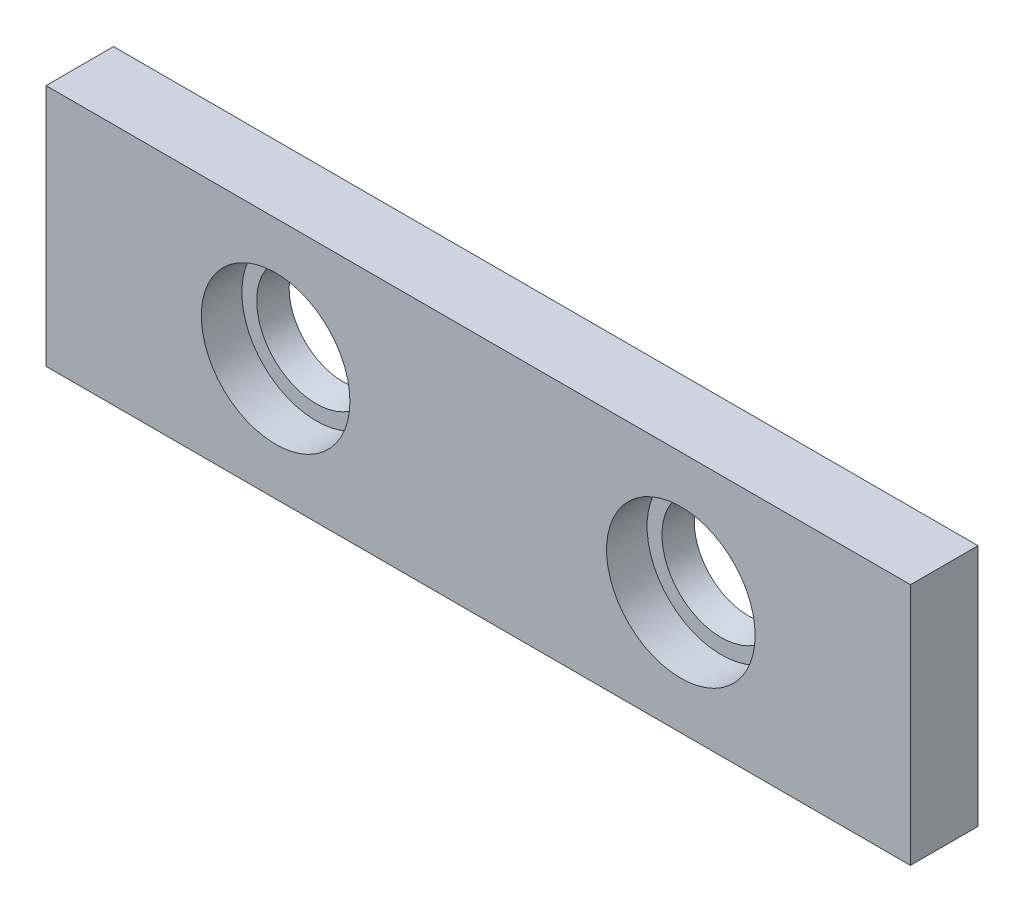
SolidWorks part; units mm, degrees
material "灰铸铁 (SN)"
ref_plane "前视基准面" through (0, 0, 0) normal (0, 0, 1) x (1, 0, 0)
ref_plane "上视基准面" through (0, 0, 0) normal (0, 1, 0) x (1, 0, 0)
ref_plane "右视基准面" through (0, 0, 0) normal (1, 0, 0) x (0, 0, -1)
sketch "草图1" plane through (0, 0, 0) normal (0, 0, 1) x (1, 0, 0)
  line L0 (3.9209, -8.1374) -> (3.9209, 9.8626)
  line L1 (-28.0791, 9.8626) -> (35.9209, 9.8626)
  line L2 (-28.0791, 9.8626) -> (-28.0791, -8.1374)
  line L3 (-28.0791, -8.1374) -> (35.9209, -8.1374)
  line L4 (35.9209, 9.8626) -> (35.9209, -8.1374)
  line L5 (35.9209, 0.8626) -> (-28.0791, 0.8626)
  line L6 (-28.0791, 0.8626) -> (-11.0791, 0.8626)
  circle A0 centre (-11.0791, 0.8626) radius 3
  circle A1 centre (18.9209, 0.8626) radius 3
  dimension "D1" = 64
  dimension "D2" = 18
  dimension "D3" = 17
extrude "凸台-拉伸1" add sketch "草图1" along normal blind 5 contours L5 A0 | L5 A0 | A1 L5 | A1 L5 | L2 L1 L4 L3 region at (18.9209, 2.1359, 0) region at (18.9209, -0.4106, 0) region at (-11.0791, -0.4106, 0) region at (-11.0791, 2.1359, 0)
ref_plane "基准面1" through (0, 0, 5) normal (0, 0, 1) x (1, 0, 0)
sketch "草图2" plane through (0, 0, 5) normal (0, 0, 1) x (1, 0, 0)
  line L0 (-11.0791, 0.8626) -> (-28.0791, 0.8626)
  line L1 (-28.0791, 9.8626) -> (-28.0791, -8.1374) construction
  line L2 (35.9209, 0.8626) -> (-28.0791, 0.8626)
  line L3 (35.9209, 9.8626) -> (35.9209, -8.1374) construction
  line L4 (18.9209, 0.8626) -> (35.9209, 0.8626)
  circle A0 centre (-11.0791, 0.8626) radius 5.5
  circle A1 centre (18.9209, 0.8626) radius 5.5
  point P8 (0, 0)
  dimension "D1" = 17
extrude "切除-拉伸1" cut sketch "草图2" against normal blind 3 contours A1 | A0
ref_plane "基准面2" through (0, 9.8626, 0) normal (0, 1, 0) x (1, 0, 0)
sketch "草图4" plane through (0, 9.8626, 0) normal (0, 1, 0) x (1, 0, 0)
  line L0 (3.9209, 0) -> (3.9209, -5)
  line L1 (-28.0791, 0) -> (35.9209, 0) construction
  line L2 (-28.0791, -5) -> (35.9209, -5) construction
  line L3 (-28.0791, -5) -> (-16.0791, -5)
  line L4 (-16.0791, -5) -> (-15.0791, 0)
  line L5 (-15.0791, 0) -> (-28.0791, 0)
  line L6 (-28.0791, 0) -> (-28.0791, -5)
  line L7 (-16.0791, -5) -> (-16.0791, 0)
  line L8 (-15.0791, 0) -> (-11.0791, 0)
  line L9 (-11.0791, 0) -> (-11.0791, -5)
  line L10 (-11.0791, -5) -> (-16.0791, -5)
  point P12 (0, 0)
  point P16 (0, 0)
  point P17 (0, 0)
  point P18 (0, 0)
  dimension "D1" = 12
  dimension "D2" = 13
  dimension "D3" = 4
ref_plane "基准面3" through (0, 0.8626, 0) normal (0, 1, 0) x (1, 0, 0)
sketch "草图5" plane through (0, 0.8626, 0) normal (0, 1, 0) x (1, 0, 0)
  line L0 (3.9209, -0.0002) -> (3.9209, -5.0002)
  line L1 (-28.0791, -5) -> (-16.0791, -5)
  line L2 (-16.0791, -5) -> (-15.0791, 0)
  line L3 (-15.0791, 0) -> (-28.0791, 0)
  line L4 (-28.0791, 0) -> (-28.0791, -5)
  line L5 (-16.0791, -5) -> (-16.0791, 0)
  line L6 (-15.0791, 0) -> (-11.0791, 0)
  line L7 (-11.0791, 0) -> (-11.0791, -5)
  line L8 (-11.0791, -5) -> (-16.0791, -5)
  line L9 (-15.0791, 0) -> (-28.0791, 0) construction
  line L10 (-16.0791, -5) -> (-15.0791, 0) construction
  line L11 (22.921, 0) -> (18.921, 0)
  line L12 (18.921, -5) -> (23.921, -5)
  line L13 (18.921, 0) -> (18.921, -5)
  line L14 (23.921, -5) -> (22.921, 0)
  point P9 (-15.5791, -5)
  point P11 (-28.0791, -5)
  point P13 (-28.0791, 0)
  point P16 (-15.5791, 0)
  point P18 (-14.0791, 0)
  point P21 (-11.0791, 0)
  point P23 (-11.0791, -5)
revolve "切除-旋转1" cut sketch "草图5" angle 360 about L7 region at (-13.3384, 0.8626, 2.5926)
revolve "切除-旋转2" cut sketch "草图5<4>" angle 360 about L13 region at (21.1803, 0.8626, 2.5926)
sketch "草图5<4>" plane through (0, 0.8626, 0) normal (0, 1, 0) x (1, 0, 0) same geometry as "草图5"
